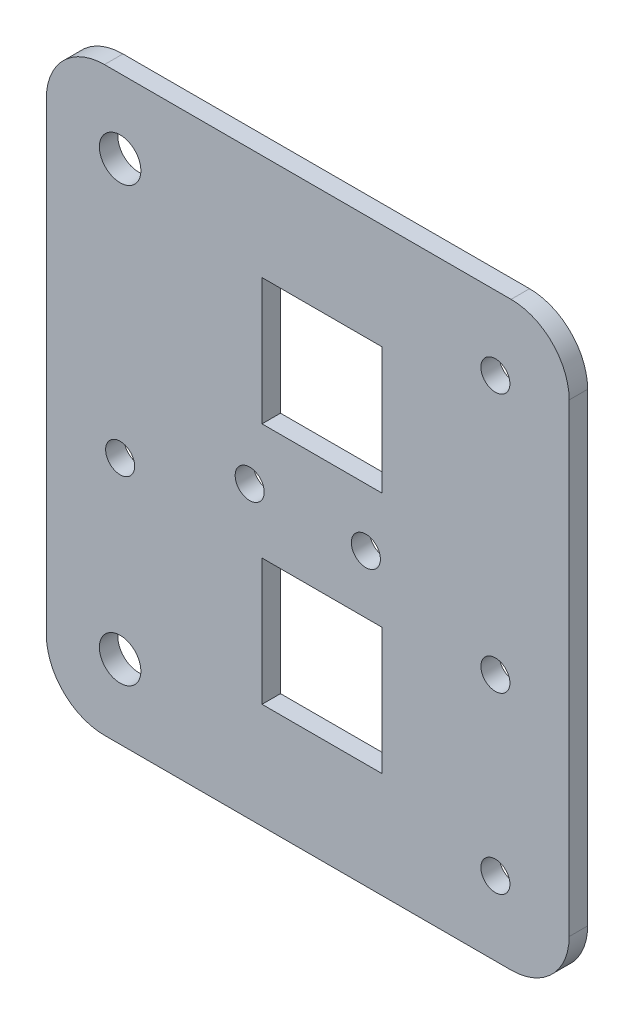
SolidWorks part; units mm, degrees
ref_plane "Front Plane" through (0, 0, 0) normal (0, 0, 1) x (1, 0, 0)
ref_plane "Top Plane" through (0, 0, 0) normal (0, 1, 0) x (1, 0, 0)
ref_plane "Right Plane" through (0, 0, 0) normal (1, 0, 0) x (0, 0, -1)
sketch "Sketch1" plane through (0, 0, 0) normal (0, 0, 1) x (1, 0, 0)
  line L0 (35, 45) -> (-35, 45) construction
  line L1 (-45, -55) -> (45, -55)
  line L2 (-45, -55) -> (-45, 45)
  line L3 (-45, 45) -> (45, 45)
  line L4 (45, -55) -> (45, 45)
  line L5 (-43.1231, -55) -> (43.1231, -55) construction
  line L6 (-45, 35) -> (-45, 25) construction
  line L7 (45, 25) -> (45, 35) construction
  circle A0 centre (32.3, -12.3) radius 2.5 construction
  circle A1 centre (32.3, -42.3) radius 2.5 construction
  circle A2 centre (-32.3, -42.3) radius 3.57 construction
  circle A3 centre (-32.3, -12.3) radius 2.5 construction
  circle A4 centre (32.3, -12.3) radius 2.5
  circle A5 centre (32.3, -42.3) radius 2.5
  circle A6 centre (-32.3, -42.3) radius 3.57
  circle A7 centre (-32.3, -12.3) radius 2.5
  circle A8 centre (-32.3, 32.3) radius 3.57 construction
  circle A9 centre (-32.3, 32.3) radius 3.57
  circle A10 centre (32.3, 32.3) radius 2.5 construction
  circle A11 centre (32.3, 32.3) radius 2.5
extrude "Boss-Extrude1" add sketch "Sketch1" against normal blind 3.18 from offset 19.16
fillet "Fillet1" radius 10 4 edges at (45, -55, 17.57) (-45, -55, 17.57) (-45, 45, 17.57) (45, 45, 17.57)
sketch "Sketch2" plane through (0, 0, 19.16) normal (0, 0, 1) x (1, 0, 0)
  line L0 (0, 45) -> (0, -55) construction
  line L1 (35, 45) -> (-35, 45) construction
  line L2 (-35, -55) -> (35, -55) construction
  line L3 (-10, -5) -> (10, -5) construction
  circle A0 centre (10, -5) radius 2.5
  circle A1 centre (-10, -5) radius 2.5
  point P9 (0, -5)
  dimension "D2" = 5
  dimension "D1" = 20
extrude "Cut-Extrude1" cut sketch "Sketch2" against normal blind 10
ref_plane "Midplane" through (0, -5, 0) normal (0, 1, 0) x (1, 0, 0)
sketch "Sketch3" plane through (0, 0, 15.98) normal (0, 0, -1) x (-1, 0, 0)
  line L1 (-10, -5) -> (-10, -15) construction
  line L2 (0, 0) -> (0, -15) construction
  line L3 (-10, -5) -> (10, -5) construction
  line L4 (7.8718, 26.811) -> (-12.7486, 26.811)
  line L5 (7.8718, -15) -> (-12.7486, -15)
  line L6 (7.8718, -15) -> (7.8718, -36.811)
  line L7 (7.8718, -36.811) -> (-12.7486, -36.811)
  line L8 (-12.7486, -15) -> (-12.7486, -36.811)
  line L9 (7.8718, 5) -> (7.8718, 26.811)
  line L10 (-12.7486, 5) -> (-12.7486, 26.811)
  line L11 (7.8718, 5) -> (-12.7486, 5)
  dimension "D1" = 10
extrude "Cut-Extrude2" cut sketch "Sketch3" against normal through all
